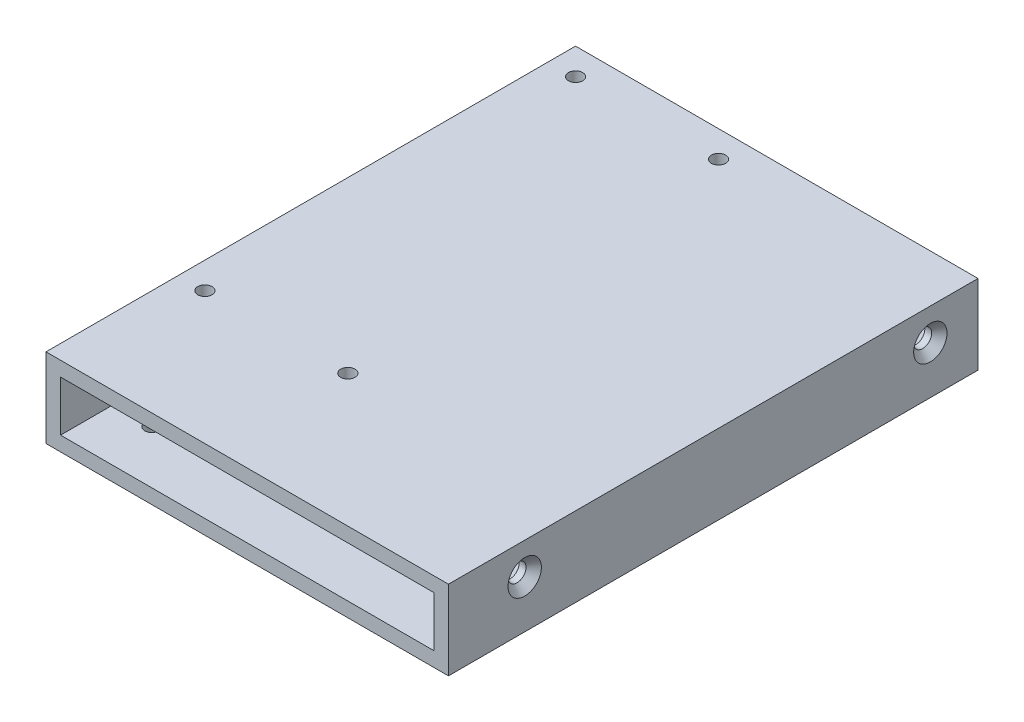
SolidWorks part; units mm, degrees
ref_plane "Plan de face" through (0, 0, 0) normal (0, 0, 1) x (1, 0, 0)
ref_plane "Plan de dessus" through (0, 0, 0) normal (0, 1, 0) x (1, 0, 0)
ref_plane "Plan de droite" through (0, 0, 0) normal (1, 0, 0) x (0, 0, -1)
sketch "Main-Sketch" plane through (0, 0, 0) normal (0, 0, 1) x (1, 0, 0)
  line L1 (0, 0) -> (76, 0)
  line L2 (0, 0) -> (0, 15)
  line L3 (0, 15) -> (76, 15)
  line L4 (76, 0) -> (76, 15)
  line L5 (2.75, 12.25) -> (73.25, 12.25)
  line L6 (2.75, 12.25) -> (2.75, 2.75)
  line L7 (2.75, 2.75) -> (73.25, 2.75)
  line L8 (73.25, 12.25) -> (73.25, 2.75)
  point P9 (38, 12.25)
  point P10 (38, 15)
  point P11 (2.75, 7.5)
  point P12 (0, 7.5)
  dimension "D1" = 76
  dimension "D2" = 15
  dimension "D3" = 70.5
  dimension "D4" = 9.5
extrude "Main-Extrusion" add sketch "Main-Sketch" along normal blind 100
hole_wizard "Fraisage pour vis à tête fraisée M31" positions "Esquisse3" profile "Esquisse4" countersink size "M3" standard "Ansi Metric" end condition through all
sketch "Esquisse3" plane through (0, 0, 0) normal (-1, 0, 0) x (0, 0, 1)
  line L0 (100, 0) -> (0, 0) construction
  line L1 (0, 15) -> (0, 0) construction
  point P0 (9, 9)
  point P9 (9.5176, 9)
  point P14 (9.3093, 8.1276)
  dimension "D1" = 9
  dimension "D2" = 9
sketch "Esquisse4" plane through (0, 9, 9) normal (0, 1, 0) x (0, 0, 1)
  line L0 (0, 0) -> (0, 76)
  line L1 (0, 76) -> (1.7, 76)
  line L2 (1.7, 76) -> (1.7, 1.45)
  line L3 (1.7, 1.45) -> (3.15, 0)
  line L5 (3.15, 0) -> (0, 0)
  line L6 (-1.7, 1.45) -> (-3.15, 0) construction
  line L11 (0, -6.35) -> (0, 107.95) construction
  dimension "Diamètre du perçage jusqu'au prochain" = 3.4
  dimension "Profondeur du perçage jusqu'au prochain" = 76
  dimension "Diamètre du fraisage entrant" = 6.3
  dimension "Angle du fraisage entrant" = 90
pattern_linear "Répétition linéaire1" count 2 spacing 76.6 along (0, 0, 1) of "Fraisage pour vis à tête fraisée M31"
hole_wizard "Fraisage pour vis à tête fraisée M32" positions "Esquisse7" profile "Esquisse8" countersink size "M3" standard "Ansi Metric" end condition through all
sketch "Esquisse7" plane through (76, 0, 0) normal (1, 0, 0) x (0, 0, -1)
  point P0 (-85.6, 9)
  point P3 (-85.5, 9)
sketch "Esquisse8" plane through (76, 9, 85.6) normal (0, 1, 0) x (0, 0, -1)
  line L0 (0, 0) -> (0, 152.5)
  line L1 (0, 152.5) -> (1.7, 152.5)
  line L2 (1.7, 152.5) -> (1.7, 1.45)
  line L3 (1.7, 1.45) -> (3.15, 0)
  line L5 (3.15, 0) -> (0, 0)
  line L6 (-1.7, 1.45) -> (-3.15, 0) construction
  line L11 (0, -6.35) -> (0, 107.95) construction
  dimension "Diamètre du perçage jusqu'au prochain" = 3.4
  dimension "Profondeur du perçage jusqu'au prochain" = 152.5
  dimension "Diamètre du fraisage entrant" = 6.3
  dimension "Angle du fraisage entrant" = 90
pattern_linear "Répétition linéaire3" count 2 spacing 76.5 along (1, 0, 0) of "Fraisage pour vis à tête fraisée M32"
hole_wizard "Fraisage pour vis à tête fraisée M33" positions "Esquisse9" profile "Esquisse10" countersink size "M3" standard "Ansi Metric" end condition through all
sketch "Esquisse9" plane through (76, 0, 0) normal (1, 0, 0) x (0, 0, -1)
  point P0 (-9, 9)
sketch "Esquisse10" plane through (76, 9, 9) normal (0, 1, 0) x (0, 0, -1)
  line L0 (0, 0) -> (0, 76)
  line L1 (0, 76) -> (1.7, 76)
  line L2 (1.7, 76) -> (1.7, 1.45)
  line L3 (1.7, 1.45) -> (3.15, 0)
  line L5 (3.15, 0) -> (0, 0)
  line L6 (-1.7, 1.45) -> (-3.15, 0) construction
  line L11 (0, -6.35) -> (0, 107.95) construction
  dimension "Diamètre du perçage jusqu'au prochain" = 3.4
  dimension "Profondeur du perçage jusqu'au prochain" = 76
  dimension "Diamètre du fraisage entrant" = 6.3
  dimension "Angle du fraisage entrant" = 90
sketch "Support-Fix-Sketch" plane through (0, 0, 0) normal (0, -1, 0) x (1, 0, 0)
  line L0 (0, 100) -> (0, 0) construction
  line L1 (76, 100) -> (76, 0) construction
  line L2 (0, 0) -> (76, 0) construction
  line L3 (0, 100) -> (76, 100) construction
  circle A0 centre (66, 90) radius 1.35
  circle A1 centre (66, 10) radius 1.35
  circle A2 centre (10, 10) radius 1.35
  circle A3 centre (10, 90) radius 1.35
  point P8 (0, 0)
  point P15 (0, 0)
  point P18 (0, 0)
  point P19 (0, 0)
  dimension "D1" = 2.7
  dimension "D2" = 10
  dimension "D3" = 10
  dimension "D4" = 10
  dimension "D5" = 10
  dimension "D6" = 56
  dimension "D7" = 80
extrude "Support-Fix-Hole" cut sketch "Support-Fix-Sketch" against normal up to next
sketch "Esquisse12" plane through (0, 15, 0) normal (0, 1, 0) x (1, 0, 0)
  line L1 (76, 0) -> (0, 0) construction
  line L2 (0, -100) -> (0, 0) construction
  circle A0 centre (32, -5) radius 1.35
  circle A1 centre (5, -5) radius 1.35
  circle A2 centre (5, -75) radius 1.35
  circle A3 centre (32, -75) radius 1.35
  point P8 (0, 0)
  point P9 (0, 0)
  point P10 (0, 0)
  point P11 (0, 0)
  dimension "D1" = 2.7
  dimension "D2" = 27
  dimension "D3" = 70
  dimension "D4" = 5
  dimension "D5" = 5
extrude "Enlèv. mat.-Extru.2" cut sketch "Esquisse12" against normal up to next
